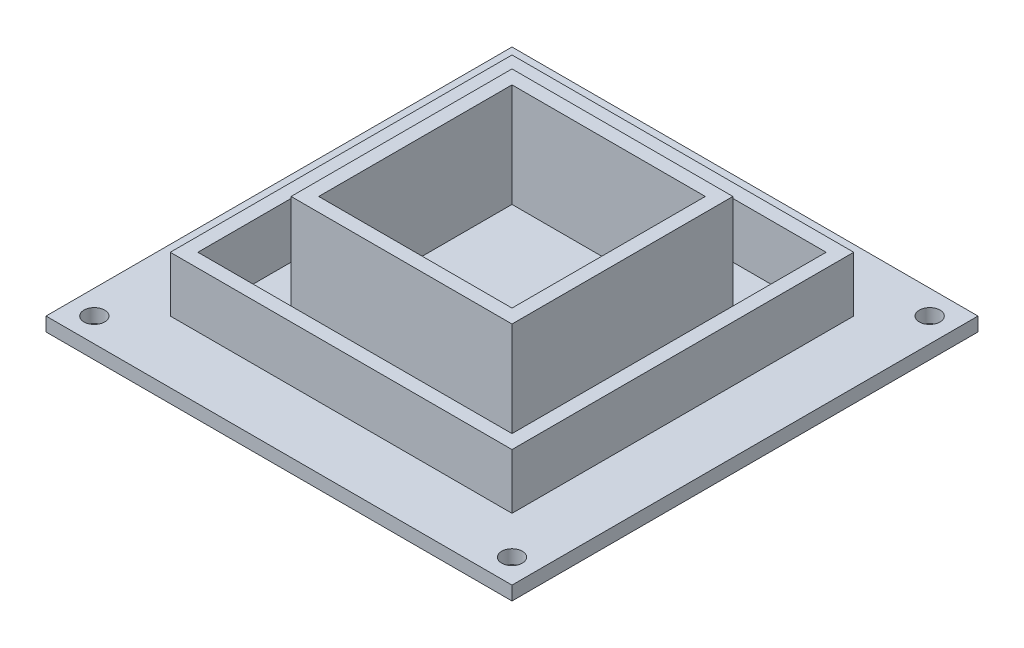
SolidWorks part; units mm, degrees
ref_plane "Front Plane" through (0, 0, 0) normal (0, 0, 1) x (1, 0, 0)
ref_plane "Top Plane" through (0, 0, 0) normal (0, 1, 0) x (1, 0, 0)
ref_plane "Right Plane" through (0, 0, 0) normal (1, 0, 0) x (0, 0, -1)
sketch "Sketch1" plane through (0, 0, 0) normal (0, 1, 0) x (1, 0, 0)
  line L0 (-7.3072, 5.9067) -> (-7.3072, -26.0933) construction
  line L1 (-23.3072, -26.0933) -> (8.6928, -26.0933)
  line L2 (-23.3072, -26.0933) -> (-23.3072, 5.9067)
  line L3 (-23.3072, 5.9067) -> (8.6928, 5.9067)
  line L4 (8.6928, -26.0933) -> (8.6928, 5.9067)
  line L5 (-23.3072, -10.0933) -> (8.6928, -10.0933) construction
  line L7 (15.4428, -32.8433) -> (-30.0572, -32.8433)
  line L8 (15.4428, -32.8433) -> (15.4428, 12.6567)
  line L9 (15.4428, 12.6567) -> (-30.0572, 12.6567)
  line L10 (-30.0572, -32.8433) -> (-30.0572, 12.6567)
  line L11 (15.4428, -32.8433) -> (-30.0572, 12.6567) construction
  line L12 (15.4428, 12.6567) -> (-30.0572, -32.8433) construction
  line L13 (-32.0572, -34.8433) -> (17.4428, -34.8433)
  line L14 (-32.0572, -34.8433) -> (-32.0572, 14.6567)
  line L15 (-32.0572, 14.6567) -> (17.4428, 14.6567)
  line L16 (17.4428, -34.8433) -> (17.4428, 14.6567)
  line L17 (-32.0572, -34.8433) -> (17.4428, 14.6567) construction
  line L18 (-32.0572, 14.6567) -> (17.4428, -34.8433) construction
  line L19 (-21.3072, -24.0933) -> (6.6928, -24.0933)
  line L20 (-21.3072, -24.0933) -> (-21.3072, 3.9067)
  line L21 (-21.3072, 3.9067) -> (6.6928, 3.9067)
  line L22 (6.6928, -24.0933) -> (6.6928, 3.9067)
  line L23 (-21.3072, -24.0933) -> (6.6928, 3.9067) construction
  line L24 (-21.3072, 3.9067) -> (6.6928, -24.0933) construction
  point P8 (-7.3072, -10.0933)
  point P13 (-7.3072, -10.0933)
  point P18 (-7.3072, -10.0933)
  dimension "D1" = 32
  dimension "D2" = 32
  dimension "D3" = 45.5
  dimension "D4" = 45.5
  dimension "D5" = 2
  dimension "D6" = 2
  dimension "D7" = 2
sketch "Sketch2" plane through (0, 0, 0) normal (0, 1, 0) x (1, 0, 0)
  line L0 (-7.3072, 23.6567) -> (-7.3072, -43.8433) construction
  line L1 (-32.0572, -34.8433) -> (17.4428, -34.8433)
  line L2 (-32.0572, -34.8433) -> (-32.0572, 14.6567)
  line L3 (-32.0572, 14.6567) -> (17.4428, 14.6567)
  line L4 (17.4428, -34.8433) -> (17.4428, 14.6567)
  line L5 (-32.0572, -34.8433) -> (17.4428, 14.6567) construction
  line L6 (-32.0572, 14.6567) -> (17.4428, -34.8433) construction
  line L7 (26.4428, -43.8433) -> (-41.0572, -43.8433)
  line L8 (26.4428, -43.8433) -> (26.4428, 23.6567)
  line L9 (26.4428, 23.6567) -> (-41.0572, 23.6567)
  line L10 (-41.0572, -43.8433) -> (-41.0572, 23.6567)
  line L11 (26.4428, -43.8433) -> (-41.0572, 23.6567) construction
  line L12 (26.4428, 23.6567) -> (-41.0572, -43.8433) construction
  line L13 (17.4428, -34.8433) -> (-32.0572, -34.8433)
  line L14 (17.4428, -34.8433) -> (17.4428, 14.6567)
  line L15 (17.4428, 14.6567) -> (-32.0572, 14.6567)
  line L16 (-32.0572, -34.8433) -> (-32.0572, 14.6567)
  line L17 (17.4428, -34.8433) -> (-32.0572, 14.6567) construction
  line L18 (17.4428, 14.6567) -> (-32.0572, -34.8433) construction
  line L19 (-41.0572, -10.0933) -> (26.4428, -10.0933) construction
  circle A0 centre (-37.5572, 20.1567) radius 1.5
  circle A1 centre (22.9428, 20.1567) radius 1.5
  circle A2 centre (22.9428, -40.3433) radius 1.5
  circle A3 centre (-37.5572, -40.3433) radius 1.5
  point P0 (-7.3072, -10.0933)
  point P5 (-7.3072, -10.0933)
  point P12 (-7.3072, -10.0933)
  dimension "D3" = 3
  dimension "D4" = 2
  dimension "D1" = 67.5
  dimension "D2" = 67.5
extrude "Boss-Extrude3" add sketch "Sketch2" along normal blind 2 contours L10 L7 L8 L9 L4 L1 L2 L3 | L1 L4 L3 L2 region at (-7.3072, 0, 10.0933) region at (-7.3072, 0, 42.8887)
extrude "Boss-Extrude4" add sketch "Sketch1" along normal blind 17 contours L1 L4 L3 L2 L22 L19 L20 L21 region at (-22.8547, 0, 10.0933)
extrude "Boss-Extrude5" add sketch "Sketch1<6>" along normal blind 10 contours L13 L16 L15 L14 L7 L10 L9 L8 region at (-31.3572, 0, 10.0933)
sketch "Sketch1<6>" plane through (0, 0, 0) normal (0, 1, 0) x (1, 0, 0) same geometry as "Sketch1"
